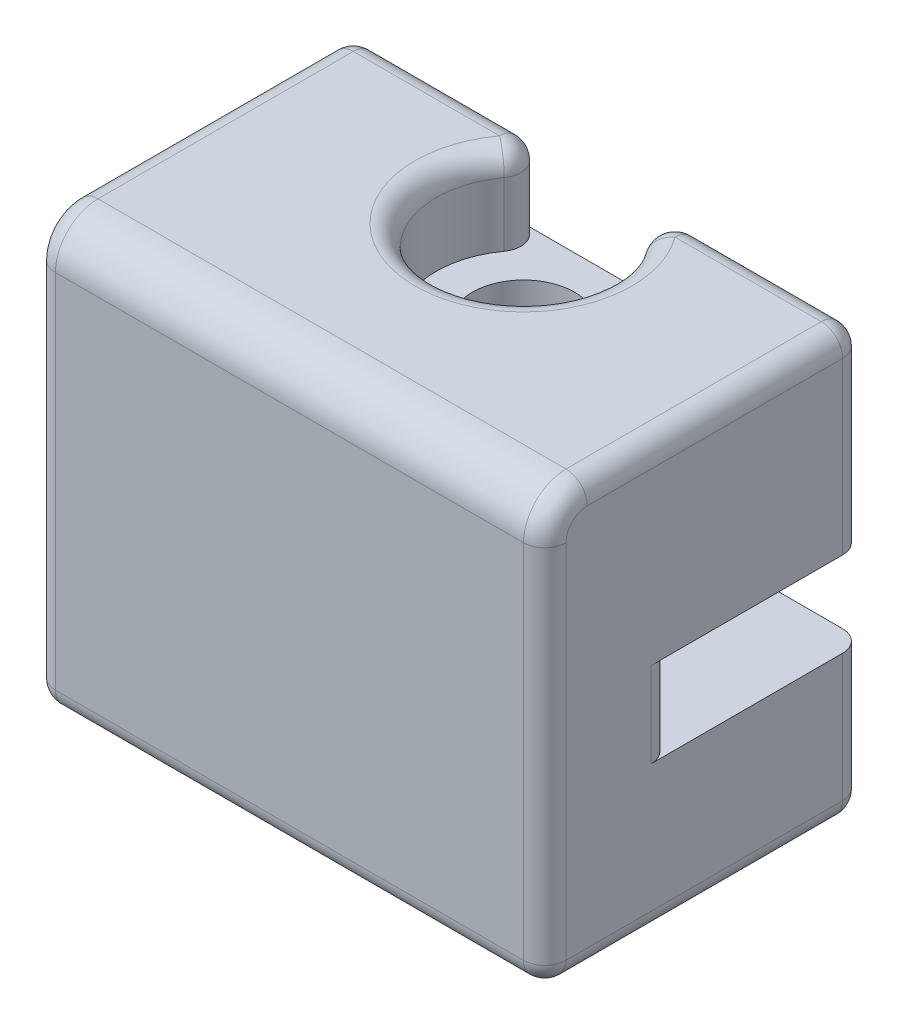
SolidWorks part; units mm, degrees
ref_plane "Front Plane" through (0, 0, 0) normal (0, 0, 1) x (1, 0, 0)
ref_plane "Top Plane" through (0, 0, 0) normal (0, 1, 0) x (1, 0, 0)
ref_plane "Right Plane" through (0, 0, 0) normal (1, 0, 0) x (0, 0, -1)
sketch "Sketch1" plane through (0, 0, 0) normal (0, 1, 0) x (1, 0, 0)
  line L5 (-6, -2.5) -> (6, -2.5)
  line L6 (-6, -2.5) -> (-6, 2.5)
  line L7 (-6, 2.5) -> (6, 2.5)
  line L8 (6, -2.5) -> (6, 2.5)
  line L9 (-6, -2.5) -> (6, 2.5) construction
  line L10 (-6, 2.5) -> (6, -2.5) construction
  point P0 (0, 0)
  dimension "D1" = 12
  dimension "D2" = 5
extrude "Boss-Extrude1" add sketch "Sketch1" along normal blind 3.5
sketch "Sketch2" plane through (0, 0, 2.5) normal (0, 0, 1) x (1, 0, 0)
  line L0 (6, 3.5) -> (6, 0) construction
  line L1 (-6, 0) -> (6, 0)
  line L2 (-6, 0) -> (-6, 5.5)
  line L3 (-6, 5.5) -> (6, 5.5)
  line L4 (6, 0) -> (6, 5.5)
  dimension "D1" = 5.5
extrude "Boss-Extrude2" add sketch "Sketch2" along normal blind 3
sketch "Sketch3" plane through (0, 5.5, 0) normal (0, 1, 0) x (1, 0, 0)
  line L1 (-6, -5.5) -> (6, -5.5)
  line L2 (-6, -5.5) -> (-6, 2.5)
  line L3 (-6, 2.5) -> (6, 2.5)
  line L4 (6, -5.5) -> (6, 2.5)
extrude "Boss-Extrude3" add sketch "Sketch3" along normal blind 4.5
sketch "Sketch4" plane through (0, 3.5, 0) normal (0, 1, 0) x (1, 0, 0)
  line L0 (6, 2.5) -> (-6, -2.5) construction
  line L1 (-6, 2.5) -> (6, -2.5) construction
  circle A0 centre (0, 0) radius 1.2
  dimension "D1" = 2.4
extrude "Cut-Extrude1" cut sketch "Sketch4" against normal blind 5 and the other way blind 7
sketch "Sketch5" plane through (0, 10, 0) normal (0, 1, 0) x (1, 0, 0)
  circle A0 centre (0, 0) radius 2.05
  dimension "D1" = 4.1
extrude "Cut-Extrude2" cut sketch "Sketch5" against normal blind 2
sketch "Sketch7" plane through (0, 0, -2.5) normal (0, 0, -1) x (-1, 0, 0)
  line L0 (6, 10) -> (6, 5.5) construction
  line L1 (6, 10) -> (-6, 10)
  line L2 (6, 10) -> (6, 0)
  line L3 (6, 0) -> (-6, 0)
  line L4 (-6, 10) -> (-6, 0)
  line L5 (-6, 3.5) -> (-6, 0) construction
  line L6 (-6, 0) -> (6, 0) construction
  line L7 (-6, 10) -> (6, 10) construction
extrude "Cut-Extrude4" cut sketch "Sketch7" against normal blind 0.5
fillet "Fillet3" radius 0.5 8 edges at (-6, 0, 1.75) (6, 0, 1.75) (0, 0, 5.5) (-6, 4.5, 2.5) (6, 4.5, 2.5) (-6, 1.75, -2) (0, 0, -2) (6, 1.75, -2)
fillet "Fillet6" radius 1 1 edges at (0, 10, 5.5)
fillet "Fillet7" radius 0.5 15 edges at (5.8536, 0.1464, 5.3536) (6, 4.75, 5.5) (6, 9.7071, 5.2071) (-5.8536, 0.1464, 5.3536) (-6, 4.75, 5.5) (-6, 9.7071, 5.2071) (6, 10, 1.25) (0, 10, 2.05) (-6, 10, 1.25) (0.45, 9, -2) (-0.45, 9, -2) (-6, 7.75, -2) (-3.225, 10, -2) (3.225, 10, -2) (6, 7.75, -2)
